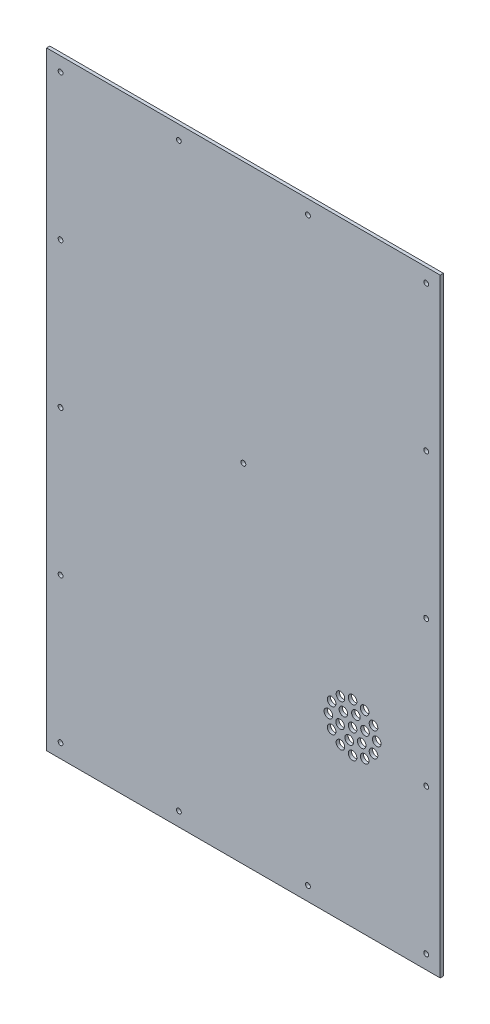
SolidWorks part; units mm, degrees
ref_plane "Спереди" through (0, 0, 0) normal (0, 0, 1) x (1, 0, 0)
ref_plane "Сверху" through (0, 0, 0) normal (0, 1, 0) x (1, 0, 0)
ref_plane "Справа" through (0, 0, 0) normal (1, 0, 0) x (0, 0, -1)
sketch "Эскиз1" plane through (0, 0, 0) normal (0, 0, 1) x (1, 0, 0)
  line L0 (0, 0) -> (366, 0)
  line L1 (0, 0) -> (0, 566)
  line L2 (366, 0) -> (366, 566)
  line L3 (0, 566) -> (366, 566)
  dimension "D1" = 566
  dimension "D2" = 366
extrude "Бобышка-Вытянуть1" add sketch "Эскиз1" along normal blind 3
sketch "Эскиз2" plane through (0, 0, 3) normal (0, 0, 1) x (1, 0, 0)
  line L0 (3, 563) -> (363, 563) construction
  line L1 (3, 563) -> (3, 3) construction
  line L2 (363, 563) -> (363, 3) construction
  line L3 (3, 3) -> (363, 3) construction
  line L4 (0, 566) -> (0, 0) construction
  line L5 (0, 0) -> (366, 0) construction
  dimension "D1" = 560
  dimension "D2" = 360
  dimension "D3" = 3
  dimension "D4" = 3
sketch "Эскиз5" plane through (0, 0, 0) normal (0, 0, -1) x (-1, 0, 0)
  line L0 (-353, 553) -> (-13, 553) construction
  line L1 (-353, 553) -> (-353, 13) construction
  line L2 (-13, 553) -> (-13, 13) construction
  line L3 (-353, 13) -> (-13, 13) construction
  line L4 (-366, 566) -> (0, 566) construction
  line L5 (-366, 0) -> (-366, 566) construction
  line L6 (0, 566) -> (0, 0) construction
  line L7 (0, 0) -> (-366, 0) construction
  line L8 (-366, 23) -> (-343, 23) construction
  line L9 (-366, 23) -> (-366, 0) construction
  line L10 (-343, 23) -> (-343, 0) construction
  line L11 (-366, 0) -> (-343, 0) construction
  line L12 (0, 0) -> (0, 23) construction
  line L13 (0, 0) -> (-23, 0) construction
  line L14 (0, 23) -> (-23, 23) construction
  line L15 (-23, 0) -> (-23, 23) construction
  line L16 (-366, 566) -> (-343, 566) construction
  line L17 (-366, 566) -> (-366, 543) construction
  line L18 (-343, 566) -> (-343, 543) construction
  line L19 (-366, 543) -> (-343, 543) construction
  line L20 (0, 566) -> (0, 543) construction
  line L21 (0, 566) -> (-23, 566) construction
  line L22 (0, 543) -> (-23, 543) construction
  line L23 (-23, 566) -> (-23, 543) construction
  line L24 (-13, 283) -> (-353, 283) construction
  line L25 (-183, 553) -> (-183, 13) construction
  line L26 (0, 0) -> (-366, 0) construction
  circle A0 centre (-353, 553) radius 2.25
  circle A1 centre (-13, 553) radius 2.25
  circle A3 centre (-243, 553) radius 2.25
  circle A4 centre (-123, 553) radius 2.25
  circle A5 centre (-353, 418) radius 2.25
  circle A6 centre (-353, 283) radius 2.25
  circle A7 centre (-353, 148) radius 2.25
  circle A8 centre (-353, 13) radius 2.25
  circle A9 centre (-123, 13) radius 2.25
  circle A10 centre (-243, 13) radius 2.25
  circle A11 centre (-13, 418) radius 2.25
  circle A12 centre (-13, 283) radius 2.25
  circle A13 centre (-13, 148) radius 2.25
  circle A14 centre (-13, 13) radius 2.25
  dimension "D13" = 4.5
  dimension "D14" = 4.5
  dimension "D15" = 110
  dimension "D17" = 4.5
  dimension "D18" = 4.5
  dimension "D19" = 110
  dimension "D22" = 135
  dimension "D23" = 135
  dimension "D24" = 110
  dimension "D25" = 5
  dimension "D26" = 135
  dimension "D27" = 110
  dimension "D28" = 120
  dimension "D29" = 4.5
  dimension "D30" = 4.5
  dimension "D1" = 13
  dimension "D2" = 13
  dimension "D3" = 13
  dimension "D4" = 13
  dimension "D5" = 23
  dimension "D6" = 23
  dimension "D7" = 23
  dimension "D8" = 23
  dimension "D9" = 23
  dimension "D10" = 23
  dimension "D11" = 23
  dimension "D12" = 23
  dimension "D21" = 5
extrude "Вырез-Вытянуть2" cut sketch "Эскиз5" against normal through all
sketch "Sketch1" plane through (0, 0, 3) normal (0, 0, 1) x (1, 0, 0)
  line L1 (343, 333) -> (23, 333) construction
  line L2 (183, 333) -> (183, 323) construction
  circle A0 centre (183, 323) radius 2.25
  dimension "D1" = 4.5
  dimension "D2" = 10
extrude "Cut-Extrude1" cut sketch "Sketch1" against normal through all
sketch "Эскиз6" plane through (0, 0, 0) normal (0, 0, -1) x (-1, 0, 0)
  line L1 (-284.5, 161) -> (-300.4099, 145.0901) construction
  line L12 (-309.5, 136) -> (-259.5, 136) construction
  line L13 (-309.5, 136) -> (-309.5, 186) construction
  line L14 (-309.5, 186) -> (-259.5, 186) construction
  line L15 (-259.5, 136) -> (-259.5, 186) construction
  line L16 (-309.5, 136) -> (-259.5, 186) construction
  line L17 (-309.5, 186) -> (-259.5, 136) construction
  circle A23 centre (-284.5, 161) radius 12 construction
  circle A25 centre (-284.5, 161) radius 22.5 construction
  circle A26 centre (-284.5, 138.5) radius 4
  circle A27 centre (-295.75, 141.5144) radius 4
  circle A28 centre (-303.9856, 149.75) radius 4
  circle A29 centre (-307, 161) radius 4
  circle A30 centre (-303.9856, 172.25) radius 4
  circle A31 centre (-295.75, 180.4856) radius 4
  circle A32 centre (-284.5, 183.5) radius 4
  circle A33 centre (-273.25, 180.4856) radius 4
  circle A34 centre (-265.0144, 172.25) radius 4
  circle A35 centre (-262, 161) radius 4
  circle A36 centre (-265.0144, 149.75) radius 4
  circle A37 centre (-273.25, 141.5144) radius 4
  circle A38 centre (-292.9853, 152.5147) radius 4
  circle A39 centre (-296.0911, 164.1058) radius 4
  circle A40 centre (-287.6058, 172.5911) radius 4
  circle A41 centre (-276.0147, 169.4853) radius 4
  circle A42 centre (-272.9089, 157.8942) radius 4
  circle A43 centre (-281.3942, 149.4089) radius 4
  circle A44 centre (-284.5, 161) radius 4
  point P40 (-296, 150)
  point P78 (-284.5, 161)
  point P80 (-292.9853, 152.5147)
  point P95 (-284.5, 161)
  dimension "D11" = 8
  dimension "D8" = 24
  dimension "D12" = 12
  dimension "D14" = 8
  dimension "D16" = 8
  dimension "D3" = 45
  dimension "D21" = 50
  dimension "D22" = 50
  dimension "D15" = 6
extrude "Вырез-Вытянуть3" cut sketch "Эскиз6" against normal through all
